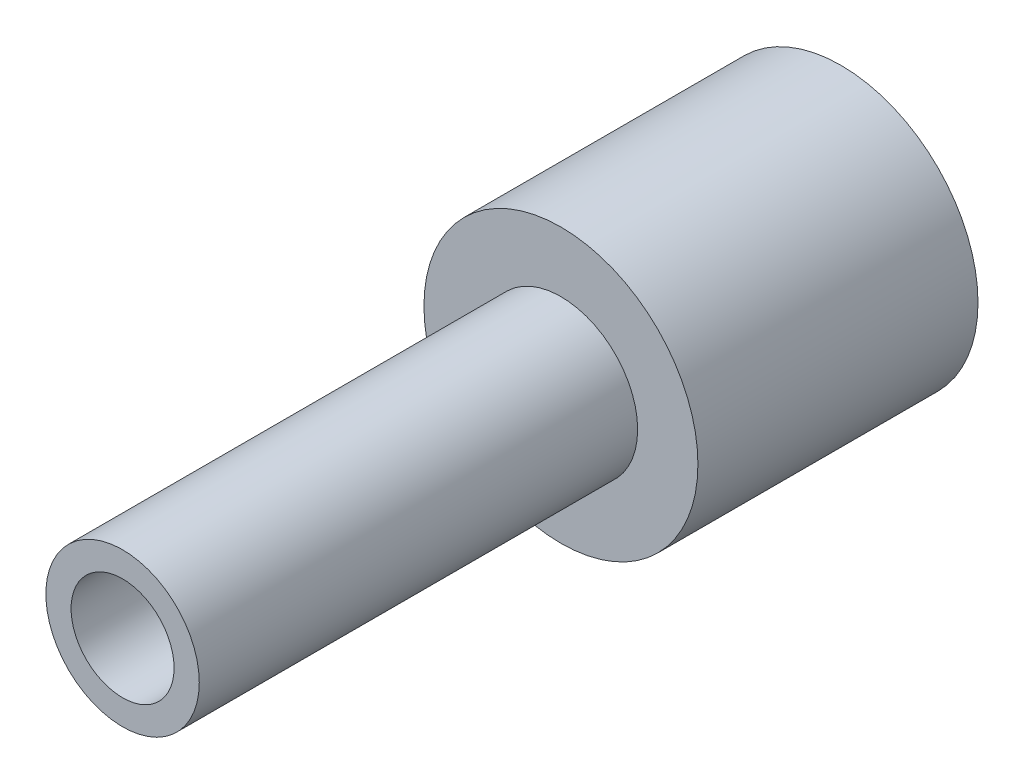
SolidWorks part; units mm, degrees
ref_plane "Front Plane" through (0, 0, 0) normal (0, 0, 1) x (1, 0, 0)
ref_plane "Top Plane" through (0, 0, 0) normal (0, 1, 0) x (1, 0, 0)
ref_plane "Right Plane" through (0, 0, 0) normal (1, 0, 0) x (0, 0, -1)
sketch "Sketch1" plane through (0, 0, 0) normal (0, 0, 1) x (1, 0, 0)
  circle A0 centre (0, 0) radius 3.175
  dimension "D1" = 6.35
extrude "Boss-Extrude1" add sketch "Sketch1" along normal blind 17.526
sketch "Sketch2" plane through (0, 0, 17.526) normal (0, 0, 1) x (1, 0, 0)
  circle A0 centre (0, 0) radius 1.778
  dimension "D1" = 3.556
extrude "Cut-Extrude1" cut sketch "Sketch2" against normal blind 10.16 flip side to cut
sketch "Sketch3" plane through (0, 0, 17.526) normal (0, 0, 1) x (1, 0, 0)
  circle A0 centre (0, 0) radius 1.1938
  dimension "D1" = 2.3876
extrude "Cut-Extrude2" cut sketch "Sketch3" against normal blind 10.16
sketch "Sketch5" plane through (0, 0, 0) normal (0, 0, -1) x (-1, 0, 0)
  circle A0 centre (0, 0) radius 0.635
  dimension "D1" = 1.27
extrude "Cut-Extrude3" cut sketch "Sketch5" against normal blind 7.62
chamfer "Chamfer1" distance 2.54 angle 19 1 edges at (3.175, 0, 0) first distance on face at (-0.635, 0, 0)
